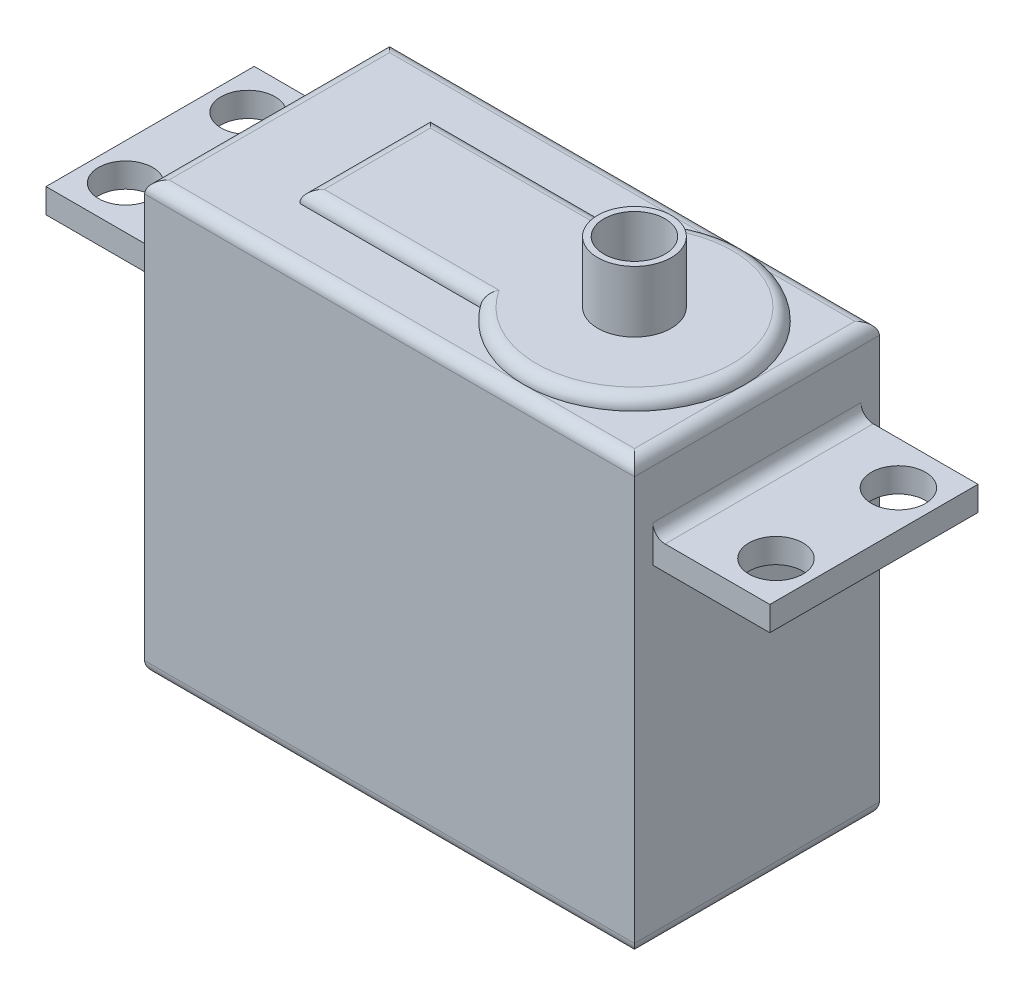
SolidWorks part; units mm, degrees
material "Nickel"
ref_plane "Front Plane" through (0, 0, 0) normal (0, 0, 1) x (1, 0, 0)
ref_plane "Top Plane" through (0, 0, 0) normal (0, 1, 0) x (1, 0, 0)
ref_plane "Right Plane" through (0, 0, 0) normal (1, 0, 0) x (0, 0, -1)
sketch "Sketch1" plane through (0, 0, 0) normal (0, 0, 1) x (1, 0, 0)
  line L1 (-20, 17.5) -> (20, 17.5)
  line L2 (-20, 17.5) -> (-20, -17.5)
  line L3 (-20, -17.5) -> (20, -17.5)
  line L4 (20, 17.5) -> (20, -17.5)
  line L5 (-20, 17.5) -> (20, -17.5) construction
  line L6 (-20, -17.5) -> (20, 17.5) construction
  point P0 (0, 0)
  dimension "D1" = 40
  dimension "D2" = 35
extrude "Boss-Extrude1" add sketch "Sketch1" along normal blind 20
fillet "Fillet1" radius 1 8 edges at (0, -17.5, 0) (-20, -17.5, 10) (20, -17.5, 10) (0, -17.5, 20) (0, 17.5, 0) (20, 17.5, 10) (0, 17.5, 20) (-20, 17.5, 10)
ref_plane "Plane1" through (0, 9.5, 0) normal (0, 1, 0) x (-1, 0, 0)
sketch "Sketch2" plane through (0, 9.5, 0) normal (0, 1, 0) x (-1, 0, 0)
  line L0 (20, 10) -> (-20, 10) construction
  line L1 (20, 20) -> (20, 0) construction
  line L2 (-20, 0) -> (-20, 20) construction
  line L3 (-20, 10) -> (-33.3686, 10) construction
  line L4 (0, 20) -> (0, 0) construction
  line L5 (-20, 20) -> (20, 20) construction
  line L6 (29.5562, 1.5) -> (20, 1.5)
  line L7 (-29.5562, 18.5) -> (-20, 18.5)
  line L8 (-29.5562, 18.5) -> (-29.5562, 1.5)
  line L9 (-29.5562, 1.5) -> (-20, 1.5)
  line L10 (-20, 18.5) -> (-20, 1.5)
  line L11 (-29.5562, 18.5) -> (-20, 1.5) construction
  line L12 (-29.5562, 1.5) -> (-20, 18.5) construction
  line L13 (20, 18.5) -> (20, 1.5)
  line L14 (29.5562, 18.5) -> (20, 18.5)
  line L15 (29.5562, 18.5) -> (29.5562, 1.5)
  circle A0 centre (-26.5562, 5) radius 2.2095
  circle A1 centre (-26.5562, 15) radius 2.2095
  circle A2 centre (26.5562, 5) radius 2.2095
  circle A3 centre (26.5562, 15) radius 2.2095
  point P12 (-24.7781, 10)
  dimension "D1" = 17
  dimension "D2" = 3
  dimension "D3" = 5
extrude "Boss-Extrude2" add sketch "Sketch2" along normal blind 2
sketch "Sketch3" plane through (0, 17.5, 0) normal (0, 1, 0) x (1, 0, 0)
  line L0 (10, -10) -> (-19, -10) construction
  line L1 (-19, -1) -> (-19, -19) construction
  line L2 (-12, -15.3326) -> (-12, -4.6674)
  line L3 (-12, -4.6674) -> (2.7499, -4.6674)
  line L4 (-12, -15.3326) -> (2.7499, -15.3326)
  circle A0 centre (10, -10) radius 9
  point P9 (-12, -10)
  dimension "D1" = 10.6652
  dimension "D2" = 22
extrude "Boss-Extrude3" add sketch "Sketch3" along normal blind 1 contours A0 | A0 L0 L2 L4 | L0 A0 L3 L2 region at (-5.211, 17.5, 12.7223) region at (-5.211, 17.5, 7.2777) region at (1.6905, 17.5, 7.2732)
sketch "Sketch4" plane through (0, 18.5, 0) normal (0, 1, 0) x (1, 0, 0)
  circle A0 centre (10, -10) radius 2.5
  circle A1 centre (10, -10) radius 3
  dimension "D1" = 6
  dimension "D2" = 5
extrude "Boss-Extrude4" add sketch "Sketch4" along normal blind 5
fillet "Fillet2" radius 1 6 edges at (20, 11.5, 10) (-20, 11.5, 10) (-12, 18.5, 10) (-4.625, 18.5, 4.6674) (19, 18.5, 10) (-4.625, 18.5, 15.3326)
